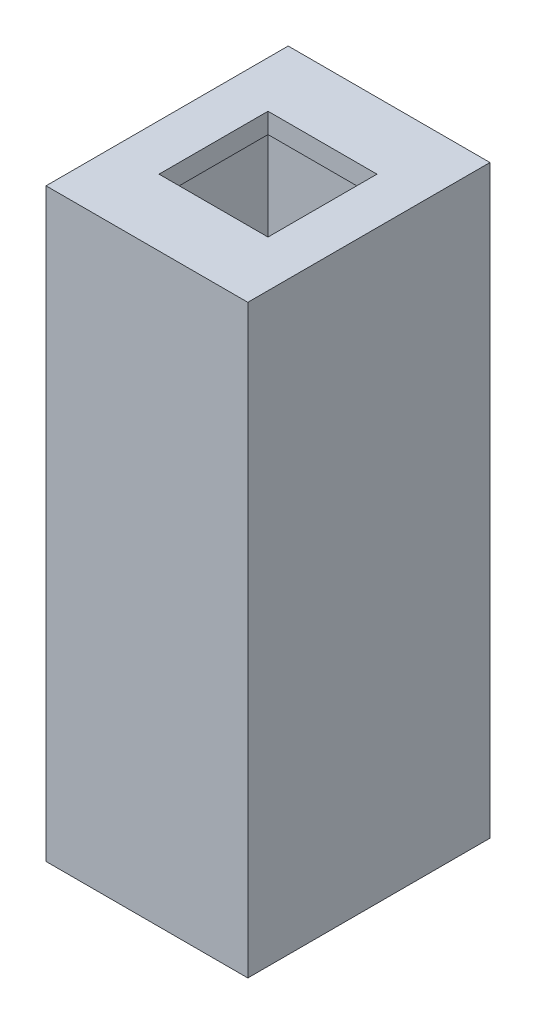
SolidWorks part; units mm, degrees
ref_plane "前视基准面" through (0, 0, 0) normal (0, 0, 1) x (1, 0, 0)
ref_plane "上视基准面" through (0, 0, 0) normal (0, 1, 0) x (1, 0, 0)
ref_plane "右视基准面" through (0, 0, 0) normal (1, 0, 0) x (0, 0, -1)
other "Configuration Table"
sketch "草图1" plane through (0, 0, 0) normal (0, 1, 0) x (1, 0, 0)
  line L1 (-3.1, 3.1) -> (3.1, 3.1)
  line L2 (-3.1, 3.1) -> (-3.1, -3.1)
  line L3 (-3.1, -3.1) -> (3.1, -3.1)
  line L4 (3.1, 3.1) -> (3.1, -3.1)
  line L5 (-3.1, 3.1) -> (3.1, -3.1) construction
  line L6 (-3.1, -3.1) -> (3.1, 3.1) construction
  line L7 (-5, 6) -> (5, 6)
  line L8 (-5, 6) -> (-5, -6)
  line L9 (-5, -6) -> (5, -6)
  line L10 (5, 6) -> (5, -6)
  line L11 (-5, 6) -> (5, -6) construction
  line L12 (-5, -6) -> (5, 6) construction
  line L13 (-2.7, -2.7) -> (2.7, -2.7)
  line L14 (-2.7, -2.7) -> (-2.7, 2.7)
  line L15 (-2.7, 2.7) -> (2.7, 2.7)
  line L16 (2.7, -2.7) -> (2.7, 2.7)
  line L17 (-2.7, -2.7) -> (2.7, 2.7) construction
  line L18 (-2.7, 2.7) -> (2.7, -2.7) construction
  point P0 (0, 0)
  point P5 (0, 0)
  point P13 (0, 0)
  dimension "D1" = 6.2
  dimension "D2" = 12
  dimension "D3" = 5.4
  dimension "D4" = 10
extrude "凸台-拉伸1" add sketch "草图1" along normal blind 29 contours L10 L7 L8 L9 L1 L4 L3 L2 region at (0, 0, -5.8438)
extrude "凸台-拉伸2" add sketch "草图1<3>" against normal blind 1 from surface contours L10 L7 L8 L9 L1 L4 L3 L2 | L4 L1 L2 L3 L16 L13 L14 L15 region at (0, 0, -3.0123) region at (0, 0, -5.8438) starting at face at (0, 29, 0)
sketch "草图1<3>" plane through (0, 0, 0) normal (0, 1, 0) x (1, 0, 0) same geometry as "草图1"
sketch "草图2" plane through (0, 0, 0) normal (0, -1, 0) x (1, 0, 0)
  line L1 (-3, -3) -> (3, -3)
  line L2 (-3, -3) -> (-3, 3)
  line L3 (-3, 3) -> (3, 3)
  line L4 (3, -3) -> (3, 3)
  line L5 (-3, -3) -> (3, 3) construction
  line L6 (-3, 3) -> (3, -3) construction
  circle A0 centre (-3.75, 4.5) radius 0.3
  circle A1 centre (3.75, -4.5) radius 0.3
  circle A2 centre (3.75, 4.5) radius 0.3
  circle A3 centre (-3.75, -4.5) radius 0.3
  point P0 (0, 0)
  dimension "D2" = 0.6
  dimension "D1" = 6
extrude "切除-拉伸1" cut sketch "草图2" against normal blind 2 contours A0 | A2 | A3 | A1
